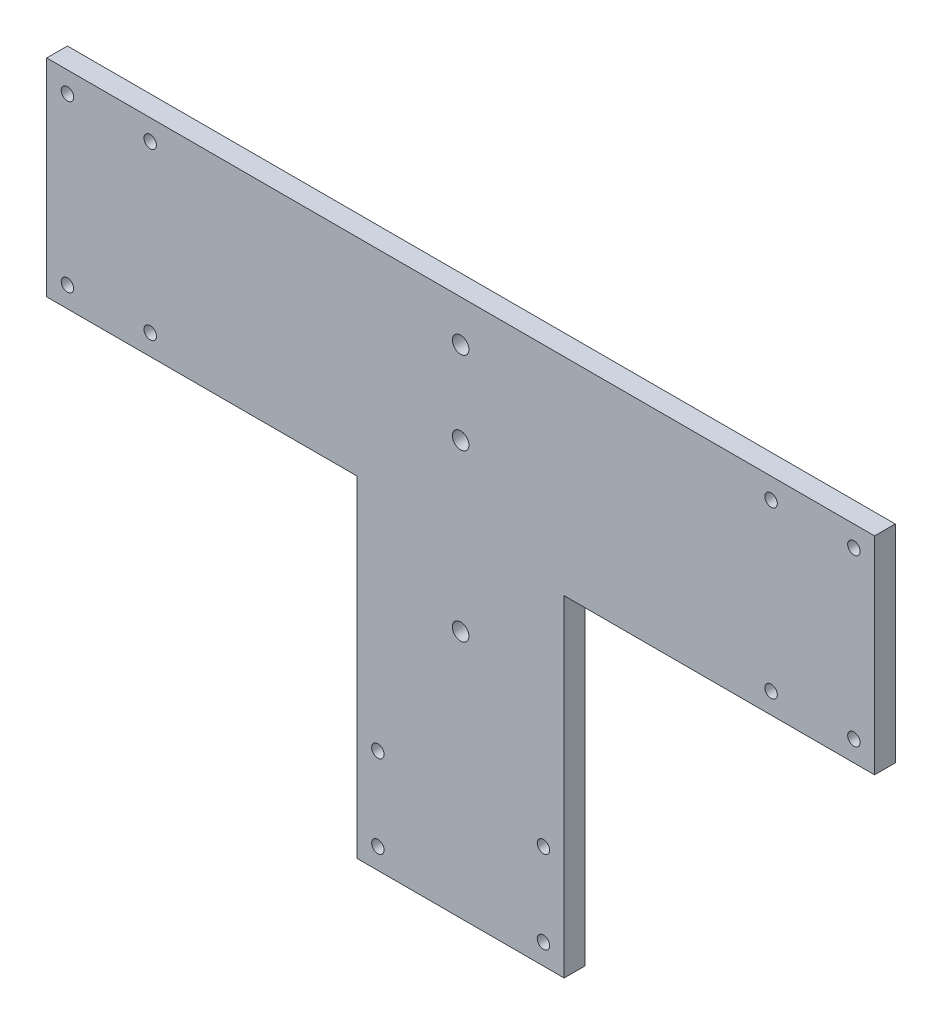
SolidWorks part; units mm, degrees
ref_plane "Plan de face" through (0, 0, 0) normal (0, 0, 1) x (1, 0, 0)
ref_plane "Plan de dessus" through (0, 0, 0) normal (0, 1, 0) x (1, 0, 0)
ref_plane "Plan de droite" through (0, 0, 0) normal (1, 0, 0) x (0, 0, -1)
sketch "Esquisse1" plane through (0, 0, 0) normal (0, 0, 1) x (1, 0, 0)
  line L0 (-25, 0) -> (25, 0) construction
  line L1 (0, 50) -> (-100, 50)
  line L2 (25, 0) -> (25, -80)
  line L3 (-70, 50) -> (-70, 0) construction
  line L4 (25, -80) -> (-25, -80)
  line L5 (-25, -50) -> (25, -50) construction
  line L6 (-25, -65) -> (25, -65) construction
  line L7 (-25, -80) -> (-25, 0)
  line L8 (0, 50) -> (0, -80) construction
  line L9 (-85, 50) -> (-85, 0) construction
  line L10 (0, 50) -> (100, 50)
  line L11 (100, 50) -> (100, 0)
  line L12 (100, 0) -> (25, 0)
  line L13 (-100, 50) -> (-100, 0)
  line L14 (-100, 0) -> (-25, 0)
  line L16 (-100, 25) -> (-70, 25) construction
  circle A0 centre (0, 20) radius 2
  circle A1 centre (0, -20) radius 2
  circle A2 centre (0, 40) radius 2
  circle A3 centre (-20, -55) radius 1.5
  circle A4 centre (20, -55) radius 1.5
  circle A5 centre (20, -75) radius 1.5
  circle A6 centre (-20, -75) radius 1.5
  circle A7 centre (-95, 45) radius 1.5
  circle A8 centre (-75, 45) radius 1.5
  circle A9 centre (-75, 5) radius 1.5
  circle A10 centre (-95, 5) radius 1.5
  circle A11 centre (75, 5) radius 1.5
  circle A12 centre (95, 5) radius 1.5
  circle A13 centre (75, 45) radius 1.5
  circle A14 centre (95, 45) radius 1.5
  point P0 (0, 0)
  point P2 (0, 0)
  dimension "D3" = 4
  dimension "D4" = 4
  dimension "D5" = 20
  dimension "D7" = 4
  dimension "D13" = 3
  dimension "D14" = 20
  dimension "D19" = 3
  dimension "D20" = 10
  dimension "D21" = 20
  dimension "D2" = 25
  dimension "D6" = 20
  dimension "D8" = 40
  dimension "D9" = 80
  dimension "D10" = 30
  dimension "D11" = 30
  dimension "D12" = 15
  dimension "D15" = 10
  dimension "D16" = 100
  dimension "D17" = 50
  dimension "D18" = 15
extrude "Boss.-Extru.1" add sketch "Esquisse1" along normal blind 5
